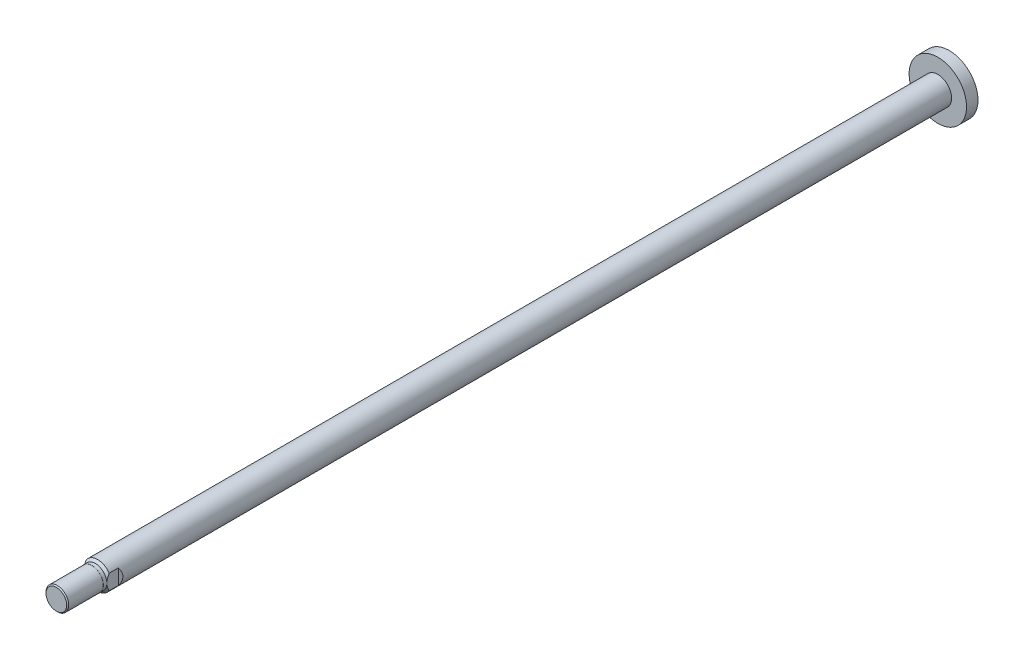
SolidWorks part; units mm, degrees
ref_plane "Front" through (0, 0, 0) normal (0, 0, 1) x (1, 0, 0)
ref_plane "Top" through (0, 0, 0) normal (0, 1, 0) x (1, 0, 0)
ref_plane "Right" through (0, 0, 0) normal (1, 0, 0) x (0, 0, -1)
sketch "Sketch1" plane through (0, 0, 0) normal (0, 0, 1) x (1, 0, 0)
  circle A0 centre (0, 0) radius 12.5
  dimension "D1" = 25
extrude "Piston" add sketch "Sketch1" along normal blind 5
sketch "Sketch2" plane through (0, 0, 0) normal (0, 0, 1) x (1, 0, 0)
  circle A0 centre (0, 0) radius 6
  dimension "D1" = 12
extrude "Rod" add sketch "Sketch2" along normal blind 389
sketch "Sketch3" plane through (0, 0, 389) normal (0, 0, 1) x (1, 0, 0)
  circle A0 centre (0, 0) radius 5
  circle A1 centre (0, 0) radius 6 construction
  circle A2 centre (0, 0) radius 6
  dimension "D1" = 10
extrude "Threads" cut sketch "Sketch3" against normal blind 18
chamfer "Rod Chamfer" distance 1 angle 45 1 edges at (5, 0, 371)
sketch "Sketch4" plane through (0, 0, 0) normal (0, 1, 0) x (1, 0, 0)
  line L0 (5, -372) -> (5, -367)
  line L1 (5, -367) -> (6, -366)
  line L2 (6, -371) -> (6, -5) construction
  line L3 (6, -366) -> (6, -372)
  line L4 (6, -372) -> (5, -372)
  line L6 (5, -372) -> (-5, -372) construction
  dimension "D1" = 5
  dimension "D2" = 45
extrude "Wrench Flat" cut sketch "Sketch4" against normal through all and the other way through all
mirror "Mirror1" about plane through (0, 0, 0) normal (1, 0, 0) of "Wrench Flat"
chamfer "Thread Chamfer" distance 0.5 angle 45 1 edges at (5, 0, 389)
sketch "Sketch5" plane through (0, 0, 389) normal (0, 0, 1) x (1, 0, 0)
  circle A0 centre (0, 0) radius 4.95
  circle A2 centre (0, 0) radius 5
  dimension "D1" = 9.9
  dimension "D2" = 10
extrude "Cut-Extrude1" cut sketch "Sketch5" against normal blind 15.5
